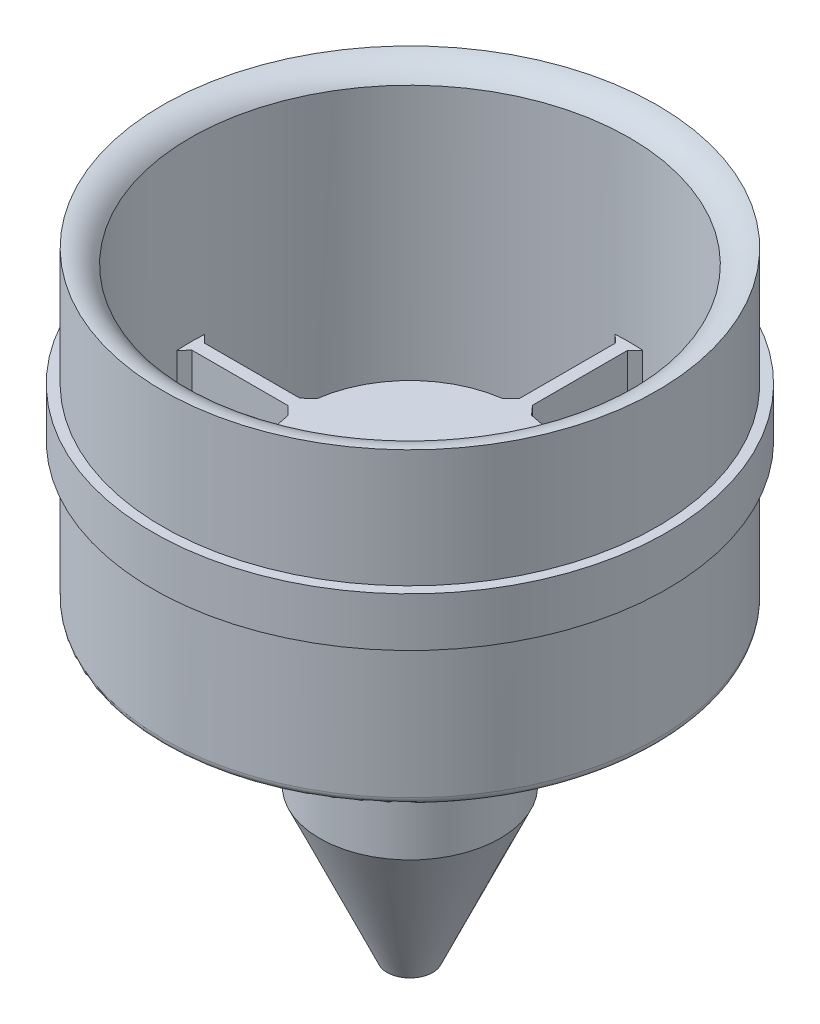
SolidWorks part; units mm, degrees
ref_plane "Front Plane" through (0, 0, 0) normal (0, 0, 1) x (1, 0, 0)
ref_plane "Top Plane" through (0, 0, 0) normal (0, 1, 0) x (1, 0, 0)
ref_plane "Right Plane" through (0, 0, 0) normal (1, 0, 0) x (0, 0, -1)
sketch "Sketch1" plane through (0, 0, 0) normal (0, 1, 0) x (1, 0, 0)
  circle A0 centre (0, 0) radius 40
  circle A1 centre (0, 0) radius 35.5
  dimension "D1" = 71
  dimension "D2" = 80
extrude "Boss-Extrude1" add sketch "Sketch1" along normal blind 50
sketch "Sketch3" plane through (0, 0, 0) normal (0, -1, 0) x (1, 0, 0)
  line L0 (0, 0) -> (0, -35.5) construction
  line L1 (-35.5, 0) -> (0, 0) construction
  line L2 (0, 0) -> (0, 35.5) construction
  line L3 (0, 0) -> (35.5, 0) construction
  line L4 (1, 0) -> (1, 35.5)
  line L5 (0, -1) -> (35.5, -1)
  line L6 (-35.5, -1) -> (0, -1)
  line L7 (-1, 0) -> (-1, -35.5)
  line L8 (-1, 0) -> (-1, 35.5)
  line L9 (0, 1) -> (35.5, 1)
  line L10 (-35.5, 1) -> (0, 1)
  line L11 (1, 0) -> (1, -35.5)
  circle A0 centre (0, 0) radius 17.5
  circle A1 centre (0, 0) radius 35.5 construction
  arc A2 (1, 0) -> (-1, 0) centre (0, 0) cw
  arc A3 (1, 35.5) -> (-1, 35.5) centre (0, 35.5) ccw
  arc A4 (0, -1) -> (0, 1) centre (0, 0) cw
  arc A5 (35.5, -1) -> (35.5, 1) centre (35.5, 0) ccw
  arc A6 (-35.5, -1) -> (-35.5, 1) centre (-35.5, 0) cw
  arc A7 (0, -1) -> (0, 1) centre (0, 0) ccw
  arc A8 (-1, 0) -> (1, 0) centre (0, 0) cw
  arc A9 (-1, -35.5) -> (1, -35.5) centre (0, -35.5) ccw
  circle M15 centre (0, 0) radius 35.5
  dimension "D1" = 35
  dimension "D2" = 1
  dimension "D3" = 1
extrude "Boss-Extrude2" add sketch "Sketch3" against normal blind 19.05 contours L11 A0 L5 | L9 A0 L4 | L8 A0 L10 | L6 A0 L7 | A2 A7 A4 | L6 A2 L7 | L11 A2 L5 | A7 L4 L9 | L8 A4 L10 | L10 A0 L6 L7 L8 | L5 A0 L9 L4 L11 | L4 A0 L8 L10 L9 | L7 A0 L11 L5 L6 | A0 L4 L8 M15 | A0 L10 L6 M15 | A0 L5 L9 M15 | A0 L7 L11 M15 region at (0.7766, 0, 0.7766) region at (9.2452, 0, 0) region at (0.7766, 0, -0.7766) region at (0, 0, 0) region at (0, 0, 9.2452) region at (7.8687, 0, 7.8687) region at (0, 0, -9.2452) region at (7.8687, 0, -7.8687) region at (-0.7766, 0, -0.7766) region at (-0.7766, 0, 0.7766) region at (0, 0, 26.4929) region at (26.4929, 0, 0) region at (0, 0, -26.4929) region at (-7.8687, 0, -7.8687) region at (-9.2452, 0, 0) region at (-7.8687, 0, 7.8687) region at (-26.4929, 0, 0)
sketch "Sketch4" plane through (0, 19.05, 0) normal (0, 1, 0) x (1, 0, 0)
  circle A0 centre (0, 0) radius 3.175
  dimension "D1" = 6.35
extrude "Cut-Extrude1" cut sketch "Sketch4" against normal blind 6.35
sketch "Sketch6" plane through (0, 0, 0) normal (1, 0, 0) x (0, 0, -1)
  line L0 (0, 0) -> (0, 50) construction
  line L1 (0, 50) -> (-40, 50) construction
  line L6 (-34.6136, 45.6984) -> (0, 45.6984)
  line L7 (0, 45.6984) -> (0, 50)
  line L8 (0, 50) -> (-40, 50)
  arc A0 (-40, 50) -> (-34.6136, 45.6984) centre (-40, 44.4768) cw
  point P3 (-32.8099, 41.9036)
  point P6 (-34.6136, 45.6984)
revolve "Cut-Revolve1" cut sketch "Sketch6" angle 360 about L0
sketch "Sketch8" plane through (0, 0, 0) normal (1, 0, 0) x (0, 0, -1)
  line L4 (0, 0) -> (-14.605, 0)
  line L7 (-14.605, 0) -> (-14.605, -25.4)
  line L8 (0, -50.8) -> (0, 0)
  line L9 (-14.605, -25.4) -> (-3.175, -50.8)
  line L10 (-3.175, -50.8) -> (0, -50.8)
  point P3 (0, 0)
  point P6 (0, 0)
  point P8 (-14.605, -21.7046)
  dimension "D1" = 3.175
  dimension "D2" = 25.4
  dimension "D3" = 11.43
  dimension "D4" = 50.8
revolve "Revolve1" add sketch "Sketch8" angle 360 about L8
chamfer "Chamfer1" distance 1.27 angle 45 1 edges at (0, -50.8, -3.175) first distance on face at (0, -50.8, -3.175)
chamfer "Chamfer2" distance 1.27 angle 45 16 edges at (-1, 9.525, 17.4714) (1, 9.525, 17.4714) (-1, 9.525, 35.4859) (1, 9.525, 35.4859) (35.4859, 9.525, -1) (35.4859, 9.525, 1) (17.4714, 9.525, 1) (17.4714, 9.525, -1) (-1, 9.525, -35.4859) (1, 9.525, -35.4859) (-1, 9.525, -17.4714) (1, 9.525, -17.4714) (-35.4859, 9.525, -1) (-35.4859, 9.525, 1) (-17.4714, 9.525, -1) (-17.4714, 9.525, 1) first distance on face at (-10.805, 9.525, 10.805) first distance on face at (1, 9.525, 26.4787) first distance on face at (-1, 9.525, 26.4787) first distance on face at (0, 9.525, 0) first distance on face at (26.4787, 9.525, 1) first distance on face at (10.805, 9.525, 10.805) first distance on face at (26.4787, 9.525, -1) first distance on face at (1, 9.525, -26.4787) first distance on face at (-1, 9.525, -26.4787) first distance on face at (10.805, 9.525, -10.805) first distance on face at (-26.4787, 9.525, -1) first distance on face at (-10.805, 9.525, -10.805) first distance on face at (-26.4787, 9.525, 1)
chamfer "Chamfer3" distance 1.27 angle 45 4 edges at (12.3411, 0, -12.4075) (12.4075, 0, 12.3411) (-12.3411, 0, 12.4075) (-12.4075, 0, -12.3411)
fillet "Fillet1" radius 1.27 6 edges at (0, 0, 14.605) (25.1136, 0, 25.0909) (25.0909, 0, -25.1136) (-25.1136, 0, -25.0909) (-25.0909, 0, 25.1136) (0, 0, 40)
sketch "Sketch9" plane through (0, 0, 0) normal (1, 0, 0) x (0, 0, -1)
  line L0 (-40, 50) -> (-40, 1.27) construction
  line L1 (-40, 30.95) -> (-41.5875, 30.95)
  line L2 (-40, 30.95) -> (-40, 23.0125)
  line L3 (-40, 23.0125) -> (-41.5875, 23.0125)
  line L4 (-41.5875, 30.95) -> (-41.5875, 23.0125)
  line L5 (0, 0) -> (0, 55.3854) construction
  line L6 (-40, 47.9123) -> (-40, 50)
  line L8 (-40.4951, 51.6212) -> (-41.0126, 51.2726)
  line L9 (-40.624, 50) -> (-40.624, 47.9123)
  line L10 (-40.624, 47.9123) -> (-40, 47.9123)
  line L11 (-40.624, 47.9123) -> (-40, 46.859)
  line L12 (-40, 50) -> (-40, 1.27) construction
  line L13 (-40, 46.859) -> (-40, 47.9123)
  arc A0 (-40, 50) -> (-40.4951, 51.6212) centre (-42.9019, 50) ccw
  arc A1 (-41.0126, 51.2726) -> (-40.624, 50) centre (-42.9019, 50) cw
  dimension "D1" = 1.5875
  dimension "D2" = 7.9375
  dimension "D3" = 19.05
revolve "Revolve2" add sketch "Sketch9" angle 360 about L5 region at (0, 26.9812, 40.7937)
